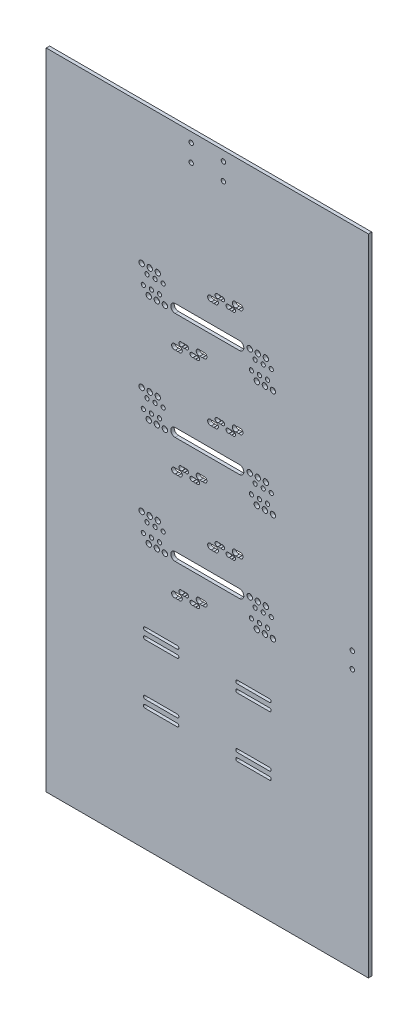
SolidWorks part; units mm, degrees
ref_plane "Front Plane" through (0, 0, 0) normal (0, 0, 1) x (1, 0, 0)
ref_plane "Top Plane" through (0, 0, 0) normal (0, 1, 0) x (1, 0, 0)
ref_plane "Right Plane" through (0, 0, 0) normal (1, 0, 0) x (0, 0, -1)
sketch "Sketch1" plane through (0, 0, 0) normal (0, 0, 1) x (1, 0, 0)
  line L1 (-165.9868, 403.6022) -> (134.0132, 403.6022)
  line L2 (-165.9868, 403.6022) -> (-165.9868, -196.3978)
  line L3 (-165.9868, -196.3978) -> (134.0132, -196.3978)
  line L4 (134.0132, 403.6022) -> (134.0132, -196.3978)
  dimension "D1" = 600
  dimension "D2" = 300
extrude "Boss-Extrude1" add sketch "Sketch1" along normal blind 3.175
sketch "Sketch2" plane through (0, 0, 0) normal (0, 0, -1) x (-1, 0, 0)
  line L0 (15.9868, -196.3978) -> (15.9868, 403.6022) construction
  line L1 (165.9868, -196.3978) -> (-134.0132, -196.3978) construction
  line L2 (-134.0132, 403.6022) -> (165.9868, 403.6022) construction
  line L3 (0.9868, 53.6022) -> (30.9868, 53.6022) construction
  line L4 (0.9868, 153.6022) -> (30.9868, 153.6022) construction
  line L5 (0.9868, 253.6022) -> (30.9868, 253.6022) construction
  point P8 (15.9868, 53.6022)
  point P11 (15.9868, 153.6022)
  dimension "D1" = 30
  dimension "D2" = 30
  dimension "D3" = 100
  dimension "D4" = 100
  dimension "D5" = 250
sketch "Sketch4" plane through (0, 0, 3.175) normal (0, 0, 1) x (1, 0, 0)
  line L0 (-45.9868, 253.6022) -> (14.0132, 253.6022) construction
  line L1 (-45.9868, 257.6022) -> (14.0132, 257.6022)
  line L2 (-45.9868, 249.6022) -> (14.0132, 249.6022)
  line L3 (-15.9868, -196.3978) -> (-15.9868, 403.6022) construction
  line L4 (-0.9868, 253.6022) -> (-30.9868, 253.6022) construction
  line L5 (-45.9868, 153.6022) -> (14.0132, 153.6022) construction
  line L6 (-45.9868, 157.6022) -> (14.0132, 157.6022)
  line L7 (-45.9868, 149.6022) -> (14.0132, 149.6022)
  line L8 (-45.9868, 53.6022) -> (14.0132, 53.6022) construction
  line L9 (-45.9868, 57.6022) -> (14.0132, 57.6022)
  line L10 (-45.9868, 49.6022) -> (14.0132, 49.6022)
  line L11 (-0.9868, 53.6022) -> (-30.9868, 53.6022) construction
  line L12 (-0.9868, 153.6022) -> (-30.9868, 153.6022) construction
  arc A0 (-45.9868, 257.6022) -> (-45.9868, 249.6022) centre (-45.9868, 253.6022) ccw
  arc A1 (14.0132, 249.6022) -> (14.0132, 257.6022) centre (14.0132, 253.6022) ccw
  arc A2 (-45.9868, 157.6022) -> (-45.9868, 149.6022) centre (-45.9868, 153.6022) ccw
  arc A3 (14.0132, 149.6022) -> (14.0132, 157.6022) centre (14.0132, 153.6022) ccw
  arc A4 (-45.9868, 57.6022) -> (-45.9868, 49.6022) centre (-45.9868, 53.6022) ccw
  arc A5 (14.0132, 49.6022) -> (14.0132, 57.6022) centre (14.0132, 53.6022) ccw
  point P2 (-15.9868, 253.6022)
  point P7 (0, 0)
  point P14 (-15.9868, 153.6022)
  point P21 (-15.9868, 53.6022)
  point P26 (30.8565, 75.9435)
  point P27 (-7.9253, 53.6022)
  point P30 (-15.9868, 53.6022)
  point P31 (-30.4018, 121.4357)
  point P32 (-15.9868, 153.6022)
  dimension "D1" = 15
  dimension "D2" = 8
  dimension "D3" = 15
  dimension "D4" = 8
  dimension "D5" = 15
  dimension "D6" = 8
extrude "Cut-Extrude1" cut sketch "Sketch4" against normal blind 10
sketch "Sketch5" plane through (0, 0, 0) normal (0, 0, -1) x (-1, 0, 0)
  line L0 (45.9868, 149.6022) -> (-14.0132, 149.6022) construction
  arc A27 (-11.0351, 86.887) -> (-13.5351, 86.887) centre (-12.2851, 84.722) ccw
  circle A34 centre (-30.1263, 32.8202) radius 2.5
  circle A35 centre (-37.6263, 32.8202) radius 2.5
  circle A36 centre (-45.1263, 32.8202) radius 2.5
  arc A37 (20.0603, 26.9076) -> (22.5603, 26.9076) centre (21.3103, 29.0726) ccw
  arc A38 (20.0603, 31.2377) -> (20.0603, 26.9076) centre (18.8103, 29.0726) ccw
  arc A39 (22.5603, 26.9076) -> (22.5603, 31.2377) centre (23.8103, 29.0726) ccw
  arc A40 (26.3551, 25.5434) -> (26.3551, 22.5501) centre (25.1051, 24.0468) ccw
  arc A41 (28.8551, 25.5434) -> (26.3551, 25.5434) centre (27.6051, 24.0468) ccw
  arc A42 (28.8551, 22.5501) -> (28.8551, 25.5434) centre (30.1051, 24.0468) ccw
  arc A43 (39.214, 26.0116) -> (39.214, 29.0049) centre (40.464, 27.5083) ccw
  arc A44 (36.714, 26.0116) -> (39.214, 26.0116) centre (37.964, 27.5083) ccw
  arc A45 (36.714, 29.0049) -> (36.714, 26.0116) centre (35.464, 27.5083) ccw
  arc A46 (43.0088, 24.6475) -> (43.0088, 20.3174) centre (41.7588, 22.4824) ccw
  arc A47 (43.0088, 20.3174) -> (45.5088, 20.3174) centre (44.2588, 22.4824) ccw
  arc A48 (45.5088, 20.3174) -> (45.5088, 24.6475) centre (46.7588, 22.4824) ccw
  circle A49 centre (-32.6024, 39.1166) radius 1.95
  circle A50 centre (-25.1024, 39.1166) radius 1.95
  circle A51 centre (-40.1024, 39.1166) radius 1.95
  circle A52 centre (-36.0672, 49.4744) radius 1.95
  circle A53 centre (-28.5672, 49.4744) radius 1.95
  circle A54 centre (-43.5672, 49.4744) radius 1.95
  circle A55 centre (-38.5434, 55.7708) radius 2.5
  circle A56 centre (-31.0434, 55.7708) radius 2.5
  circle A57 centre (-23.5434, 55.7708) radius 2.5
  arc A58 (-13.5351, 82.5569) -> (-11.0351, 82.5569) centre (-12.2851, 84.722) ccw
  arc A59 (-13.5351, 86.887) -> (-13.5351, 82.5569) centre (-14.7851, 84.722) ccw
  arc A60 (-11.0351, 82.5569) -> (-11.0351, 86.887) centre (-9.7851, 84.722) ccw
  arc A61 (-7.2404, 81.1928) -> (-7.2404, 78.1994) centre (-8.4904, 79.6961) ccw
  arc A62 (-7.2404, 78.1994) -> (-4.7404, 78.1994) centre (-5.9904, 79.6961) ccw
  arc A63 (-4.7404, 78.1994) -> (-4.7404, 81.1928) centre (-3.4904, 79.6961) ccw
  arc A64 (3.1186, 84.6543) -> (3.1186, 81.6609) centre (1.8686, 83.1576) ccw
  arc A65 (3.1186, 81.6609) -> (5.6186, 81.6609) centre (4.3686, 83.1576) ccw
  arc A66 (5.6186, 81.6609) -> (5.6186, 84.6543) centre (6.8686, 83.1576) ccw
  arc A67 (9.4133, 80.2968) -> (9.4133, 75.9667) centre (8.1633, 78.1317) ccw
  arc A68 (9.4133, 75.9667) -> (11.9133, 75.9667) centre (10.6633, 78.1317) ccw
  arc A69 (11.9133, 75.9667) -> (11.9133, 80.2968) centre (13.1633, 78.1317) ccw
  circle A70 centre (62.0999, 74.3842) radius 2.5
  circle A71 centre (69.5999, 74.3842) radius 2.5
  circle A72 centre (77.0999, 74.3842) radius 2.5
  circle A73 centre (57.0761, 68.0878) radius 1.95
  circle A74 centre (64.5761, 68.0878) radius 1.95
  circle A75 centre (72.0761, 68.0878) radius 1.95
  circle A76 centre (60.5409, 57.7299) radius 1.95
  circle A77 centre (68.0409, 57.7299) radius 1.95
  circle A78 centre (75.5409, 57.7299) radius 1.95
  circle A79 centre (70.5171, 51.4336) radius 2.5
  circle A80 centre (63.0171, 51.4336) radius 2.5
  circle A81 centre (55.5171, 51.4336) radius 2.5
  arc A82 (-4.7404, 81.1928) -> (-7.2404, 81.1928) centre (-5.9904, 79.6961) ccw
  arc A83 (5.6186, 84.6543) -> (3.1186, 84.6543) centre (4.3686, 83.1576) ccw
  arc A84 (11.9133, 80.2968) -> (9.4133, 80.2968) centre (10.6633, 78.1317) ccw
  arc A85 (39.214, 29.0049) -> (36.714, 29.0049) centre (37.964, 27.5083) ccw
  arc A86 (45.5088, 24.6475) -> (43.0088, 24.6475) centre (44.2588, 22.4824) ccw
  arc A87 (26.3551, 22.5501) -> (28.8551, 22.5501) centre (27.6051, 24.0468) ccw
  arc A88 (22.5603, 31.2377) -> (20.0603, 31.2377) centre (21.3103, 29.0726) ccw
  arc A89 (-11.0351, 186.887) -> (-13.5351, 186.887) centre (-12.2851, 184.722) ccw
  circle A90 centre (-30.1263, 132.8202) radius 2.5
  circle A91 centre (-37.6263, 132.8202) radius 2.5
  circle A92 centre (-45.1263, 132.8202) radius 2.5
  arc A93 (20.0603, 126.9076) -> (22.5603, 126.9076) centre (21.3103, 129.0726) ccw
  arc A94 (20.0603, 131.2377) -> (20.0603, 126.9076) centre (18.8103, 129.0726) ccw
  arc A95 (22.5603, 126.9076) -> (22.5603, 131.2377) centre (23.8103, 129.0726) ccw
  arc A96 (26.3551, 125.5434) -> (26.3551, 122.5501) centre (25.1051, 124.0468) ccw
  arc A97 (28.8551, 125.5434) -> (26.3551, 125.5434) centre (27.6051, 124.0468) ccw
  arc A98 (28.8551, 122.5501) -> (28.8551, 125.5434) centre (30.1051, 124.0468) ccw
  arc A99 (39.214, 126.0116) -> (39.214, 129.0049) centre (40.464, 127.5083) ccw
  arc A100 (36.714, 126.0116) -> (39.214, 126.0116) centre (37.964, 127.5083) ccw
  arc A101 (36.714, 129.0049) -> (36.714, 126.0116) centre (35.464, 127.5083) ccw
  arc A102 (43.0088, 124.6475) -> (43.0088, 120.3174) centre (41.7588, 122.4824) ccw
  arc A103 (43.0088, 120.3174) -> (45.5088, 120.3174) centre (44.2588, 122.4824) ccw
  arc A104 (45.5088, 120.3174) -> (45.5088, 124.6475) centre (46.7588, 122.4824) ccw
  circle A105 centre (-32.6024, 139.1166) radius 1.95
  circle A106 centre (-25.1024, 139.1166) radius 1.95
  circle A107 centre (-40.1024, 139.1166) radius 1.95
  circle A108 centre (-36.0672, 149.4744) radius 1.95
  circle A109 centre (-28.5672, 149.4744) radius 1.95
  circle A110 centre (-43.5672, 149.4744) radius 1.95
  circle A111 centre (-38.5434, 155.7708) radius 2.5
  circle A112 centre (-31.0434, 155.7708) radius 2.5
  circle A113 centre (-23.5434, 155.7708) radius 2.5
  arc A114 (-13.5351, 182.5569) -> (-11.0351, 182.5569) centre (-12.2851, 184.722) ccw
  arc A115 (-13.5351, 186.887) -> (-13.5351, 182.5569) centre (-14.7851, 184.722) ccw
  arc A116 (-11.0351, 182.5569) -> (-11.0351, 186.887) centre (-9.7851, 184.722) ccw
  arc A117 (-7.2404, 181.1928) -> (-7.2404, 178.1994) centre (-8.4904, 179.6961) ccw
  arc A118 (-7.2404, 178.1994) -> (-4.7404, 178.1994) centre (-5.9904, 179.6961) ccw
  arc A119 (-4.7404, 178.1994) -> (-4.7404, 181.1928) centre (-3.4904, 179.6961) ccw
  arc A120 (3.1186, 184.6543) -> (3.1186, 181.6609) centre (1.8686, 183.1576) ccw
  arc A121 (3.1186, 181.6609) -> (5.6186, 181.6609) centre (4.3686, 183.1576) ccw
  arc A122 (5.6186, 181.6609) -> (5.6186, 184.6543) centre (6.8686, 183.1576) ccw
  arc A123 (9.4133, 180.2968) -> (9.4133, 175.9667) centre (8.1633, 178.1317) ccw
  arc A124 (9.4133, 175.9667) -> (11.9133, 175.9667) centre (10.6633, 178.1317) ccw
  arc A125 (11.9133, 175.9667) -> (11.9133, 180.2968) centre (13.1633, 178.1317) ccw
  circle A126 centre (62.0999, 174.3842) radius 2.5
  circle A127 centre (69.5999, 174.3842) radius 2.5
  circle A128 centre (77.0999, 174.3842) radius 2.5
  circle A129 centre (57.0761, 168.0878) radius 1.95
  circle A130 centre (64.5761, 168.0878) radius 1.95
  circle A131 centre (72.0761, 168.0878) radius 1.95
  circle A132 centre (60.5409, 157.7299) radius 1.95
  circle A133 centre (68.0409, 157.7299) radius 1.95
  circle A134 centre (75.5409, 157.7299) radius 1.95
  circle A135 centre (70.5171, 151.4336) radius 2.5
  circle A136 centre (63.0171, 151.4336) radius 2.5
  circle A137 centre (55.5171, 151.4336) radius 2.5
  arc A138 (-4.7404, 181.1928) -> (-7.2404, 181.1928) centre (-5.9904, 179.6961) ccw
  arc A139 (5.6186, 184.6543) -> (3.1186, 184.6543) centre (4.3686, 183.1576) ccw
  arc A140 (11.9133, 180.2968) -> (9.4133, 180.2968) centre (10.6633, 178.1317) ccw
  arc A141 (39.214, 129.0049) -> (36.714, 129.0049) centre (37.964, 127.5083) ccw
  arc A142 (45.5088, 124.6475) -> (43.0088, 124.6475) centre (44.2588, 122.4824) ccw
  arc A143 (26.3551, 122.5501) -> (28.8551, 122.5501) centre (27.6051, 124.0468) ccw
  arc A144 (22.5603, 131.2377) -> (20.0603, 131.2377) centre (21.3103, 129.0726) ccw
  arc A145 (-11.0351, 286.887) -> (-13.5351, 286.887) centre (-12.2851, 284.722) ccw
  circle A146 centre (-30.1263, 232.8202) radius 2.5
  circle A147 centre (-37.6263, 232.8202) radius 2.5
  circle A148 centre (-45.1263, 232.8202) radius 2.5
  arc A149 (20.0603, 226.9076) -> (22.5603, 226.9076) centre (21.3103, 229.0726) ccw
  arc A150 (20.0603, 231.2377) -> (20.0603, 226.9076) centre (18.8103, 229.0726) ccw
  arc A151 (22.5603, 226.9076) -> (22.5603, 231.2377) centre (23.8103, 229.0726) ccw
  arc A152 (26.3551, 225.5434) -> (26.3551, 222.5501) centre (25.1051, 224.0468) ccw
  arc A153 (28.8551, 225.5434) -> (26.3551, 225.5434) centre (27.6051, 224.0468) ccw
  arc A154 (28.8551, 222.5501) -> (28.8551, 225.5434) centre (30.1051, 224.0468) ccw
  arc A155 (39.214, 226.0116) -> (39.214, 229.0049) centre (40.464, 227.5083) ccw
  arc A156 (36.714, 226.0116) -> (39.214, 226.0116) centre (37.964, 227.5083) ccw
  arc A157 (36.714, 229.0049) -> (36.714, 226.0116) centre (35.464, 227.5083) ccw
  arc A158 (43.0088, 224.6475) -> (43.0088, 220.3174) centre (41.7588, 222.4824) ccw
  arc A159 (43.0088, 220.3174) -> (45.5088, 220.3174) centre (44.2588, 222.4824) ccw
  arc A160 (45.5088, 220.3174) -> (45.5088, 224.6475) centre (46.7588, 222.4824) ccw
  circle A161 centre (-32.6024, 239.1166) radius 1.95
  circle A162 centre (-25.1024, 239.1166) radius 1.95
  circle A163 centre (-40.1024, 239.1166) radius 1.95
  circle A164 centre (-36.0672, 249.4744) radius 1.95
  circle A165 centre (-28.5672, 249.4744) radius 1.95
  circle A166 centre (-43.5672, 249.4744) radius 1.95
  circle A167 centre (-38.5434, 255.7708) radius 2.5
  circle A168 centre (-31.0434, 255.7708) radius 2.5
  circle A169 centre (-23.5434, 255.7708) radius 2.5
  arc A170 (-13.5351, 282.5569) -> (-11.0351, 282.5569) centre (-12.2851, 284.722) ccw
  arc A171 (-13.5351, 286.887) -> (-13.5351, 282.5569) centre (-14.7851, 284.722) ccw
  arc A172 (-11.0351, 282.5569) -> (-11.0351, 286.887) centre (-9.7851, 284.722) ccw
  arc A173 (-7.2404, 281.1928) -> (-7.2404, 278.1994) centre (-8.4904, 279.6961) ccw
  arc A174 (-7.2404, 278.1994) -> (-4.7404, 278.1994) centre (-5.9904, 279.6961) ccw
  arc A175 (-4.7404, 278.1994) -> (-4.7404, 281.1928) centre (-3.4904, 279.6961) ccw
  arc A176 (3.1186, 284.6543) -> (3.1186, 281.6609) centre (1.8686, 283.1576) ccw
  arc A177 (3.1186, 281.6609) -> (5.6186, 281.6609) centre (4.3686, 283.1576) ccw
  arc A178 (5.6186, 281.6609) -> (5.6186, 284.6543) centre (6.8686, 283.1576) ccw
  arc A179 (9.4133, 280.2968) -> (9.4133, 275.9667) centre (8.1633, 278.1317) ccw
  arc A180 (9.4133, 275.9667) -> (11.9133, 275.9667) centre (10.6633, 278.1317) ccw
  arc A181 (11.9133, 275.9667) -> (11.9133, 280.2968) centre (13.1633, 278.1317) ccw
  circle A182 centre (62.0999, 274.3842) radius 2.5
  circle A183 centre (69.5999, 274.3842) radius 2.5
  circle A184 centre (77.0999, 274.3842) radius 2.5
  circle A185 centre (57.0761, 268.0878) radius 1.95
  circle A186 centre (64.5761, 268.0878) radius 1.95
  circle A187 centre (72.0761, 268.0878) radius 1.95
  circle A188 centre (60.5409, 257.7299) radius 1.95
  circle A189 centre (68.0409, 257.7299) radius 1.95
  circle A190 centre (75.5409, 257.7299) radius 1.95
  circle A191 centre (70.5171, 251.4336) radius 2.5
  circle A192 centre (63.0171, 251.4336) radius 2.5
  circle A193 centre (55.5171, 251.4336) radius 2.5
  arc A194 (-4.7404, 281.1928) -> (-7.2404, 281.1928) centre (-5.9904, 279.6961) ccw
  arc A195 (5.6186, 284.6543) -> (3.1186, 284.6543) centre (4.3686, 283.1576) ccw
  arc A196 (11.9133, 280.2968) -> (9.4133, 280.2968) centre (10.6633, 278.1317) ccw
  arc A197 (39.214, 229.0049) -> (36.714, 229.0049) centre (37.964, 227.5083) ccw
  arc A198 (45.5088, 224.6475) -> (43.0088, 224.6475) centre (44.2588, 222.4824) ccw
  arc A199 (26.3551, 222.5501) -> (28.8551, 222.5501) centre (27.6051, 224.0468) ccw
  arc A200 (22.5603, 231.2377) -> (20.0603, 231.2377) centre (21.3103, 229.0726) ccw
  dimension "D1" = 3
extrude "Cut-Extrude4" cut sketch "Sketch5" against normal blind 10
sketch "Sketch6" plane through (0, 0, 0) normal (0, 0, -1) x (-1, 0, 0)
  circle A0 centre (0.9868, 394.6022) radius 2.05
  circle A1 centre (30.9868, 394.6022) radius 2.05
  circle A2 centre (30.9868, 378.6022) radius 2.05
  circle A3 centre (0.9868, 378.6022) radius 2.05
  dimension "D1" = 4.1
extrude "Cut-Extrude5" cut sketch "Sketch6" against normal blind 51
sketch "Sketch7" plane through (0, 0, 0) normal (0, 0, -1) x (-1, 0, 0)
  line L0 (-42.0132, -26.0503) -> (-12.0132, -26.0503) construction
  line L1 (-42.0132, -24.5503) -> (-12.0132, -24.5503)
  line L2 (-42.0132, -27.5503) -> (-12.0132, -27.5503)
  line L3 (-62.0132, -72.5503) -> (-62.0132, -27.5503) construction
  line L6 (-42.0132, -18.7418) -> (-12.0132, -18.7418) construction
  line L7 (-42.0132, -17.2418) -> (-12.0132, -17.2418)
  line L8 (-42.0132, -20.2418) -> (-12.0132, -20.2418)
  line L9 (-59.0132, -24.5503) -> (90.9868, -24.5503) construction
  line L10 (43.9868, -26.0503) -> (73.9868, -26.0503) construction
  line L11 (43.9868, -24.5503) -> (73.9868, -24.5503)
  line L12 (43.9868, -27.5503) -> (73.9868, -27.5503)
  line L13 (43.9868, -18.7418) -> (73.9868, -18.7418) construction
  line L14 (43.9868, -17.2418) -> (73.9868, -17.2418)
  line L15 (43.9868, -20.2418) -> (73.9868, -20.2418)
  line L16 (43.9868, -81.3587) -> (73.9868, -81.3587) construction
  line L17 (43.9868, -79.8587) -> (73.9868, -79.8587)
  line L18 (43.9868, -82.8587) -> (73.9868, -82.8587)
  line L19 (43.9868, -74.0503) -> (73.9868, -74.0503) construction
  line L20 (43.9868, -72.5503) -> (73.9868, -72.5503)
  line L21 (43.9868, -75.5503) -> (73.9868, -75.5503)
  line L22 (-42.0132, -81.3587) -> (-12.0132, -81.3587) construction
  line L23 (-42.0132, -79.8587) -> (-12.0132, -79.8587)
  line L24 (-42.0132, -82.8587) -> (-12.0132, -82.8587)
  line L25 (-42.0132, -74.0503) -> (-12.0132, -74.0503) construction
  line L26 (-42.0132, -72.5503) -> (-12.0132, -72.5503)
  line L27 (-42.0132, -75.5503) -> (-12.0132, -75.5503)
  line L28 (93.9868, -72.5503) -> (93.9868, -27.5503) construction
  line L29 (90.9868, -75.5503) -> (-59.0132, -75.5503) construction
  arc A0 (-42.0132, -24.5503) -> (-42.0132, -27.5503) centre (-42.0132, -26.0503) ccw
  arc A1 (-12.0132, -27.5503) -> (-12.0132, -24.5503) centre (-12.0132, -26.0503) ccw
  arc A4 (-42.0132, -17.2418) -> (-42.0132, -20.2418) centre (-42.0132, -18.7418) ccw
  arc A5 (-12.0132, -20.2418) -> (-12.0132, -17.2418) centre (-12.0132, -18.7418) ccw
  arc A6 (43.9868, -24.5503) -> (43.9868, -27.5503) centre (43.9868, -26.0503) ccw
  arc A7 (73.9868, -27.5503) -> (73.9868, -24.5503) centre (73.9868, -26.0503) ccw
  arc A8 (43.9868, -17.2418) -> (43.9868, -20.2418) centre (43.9868, -18.7418) ccw
  arc A9 (73.9868, -20.2418) -> (73.9868, -17.2418) centre (73.9868, -18.7418) ccw
  arc A10 (43.9868, -79.8587) -> (43.9868, -82.8587) centre (43.9868, -81.3587) ccw
  arc A11 (73.9868, -82.8587) -> (73.9868, -79.8587) centre (73.9868, -81.3587) ccw
  arc A12 (43.9868, -72.5503) -> (43.9868, -75.5503) centre (43.9868, -74.0503) ccw
  arc A13 (73.9868, -75.5503) -> (73.9868, -72.5503) centre (73.9868, -74.0503) ccw
  arc A14 (-42.0132, -79.8587) -> (-42.0132, -82.8587) centre (-42.0132, -81.3587) ccw
  arc A15 (-12.0132, -82.8587) -> (-12.0132, -79.8587) centre (-12.0132, -81.3587) ccw
  arc A16 (-42.0132, -72.5503) -> (-42.0132, -75.5503) centre (-42.0132, -74.0503) ccw
  arc A17 (-12.0132, -75.5503) -> (-12.0132, -72.5503) centre (-12.0132, -74.0503) ccw
  point P2 (-27.0132, -26.0503)
  point P7 (0, 0)
  point P8 (0, 0)
  point P9 (0, 0)
  point P14 (-27.0132, -18.7418)
  point P23 (58.9868, -26.0503)
  point P28 (58.9868, -18.7418)
  point P37 (58.9868, -81.3587)
  point P42 (58.9868, -74.0503)
  point P51 (-27.0132, -81.3587)
  point P56 (-27.0132, -74.0503)
  point P63 (0, 0)
  point P64 (0, 0)
  point P65 (0, 0)
  point P66 (75.0984, -18.7418)
  point P71 (0, 0)
  point P72 (0, 0)
  point P73 (0, 0)
  dimension "D1" = 3
  dimension "D2" = 30
  dimension "D3" = 4.3085
  dimension "D4" = 3
  dimension "D5" = 20
  dimension "D6" = 3
  dimension "D7" = 30
  dimension "D8" = 4.3085
  dimension "D9" = 3
  dimension "D10" = 3
  dimension "D11" = 30
  dimension "D12" = 4.3085
  dimension "D13" = 3
  dimension "D14" = 3
  dimension "D15" = 30
  dimension "D16" = 4.3085
  dimension "D17" = 3
  dimension "D18" = 20
extrude "Cut-Extrude6" cut sketch "Sketch7" against normal blind 51
sketch "Sketch8" plane through (0, 0, 0) normal (0, 0, -1) x (-1, 0, 0)
  circle A0 centre (-119.0132, 60.1072) radius 2.1
  circle A1 centre (-119.0132, 45.1072) radius 2.1
  dimension "D1" = 4.2
extrude "Cut-Extrude7" cut sketch "Sketch8" against normal blind 67
